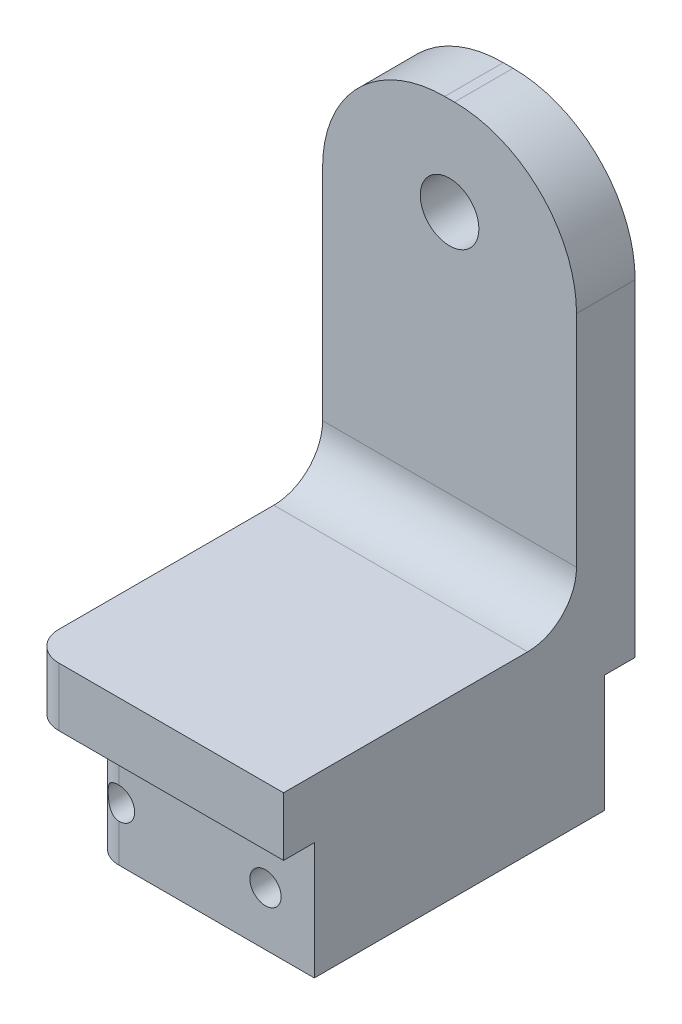
SolidWorks part; units mm, degrees
ref_plane "Front Plane" through (0, 0, 0) normal (0, 0, 1) x (1, 0, 0)
ref_plane "Top Plane" through (0, 0, 0) normal (0, 1, 0) x (1, 0, 0)
ref_plane "Right Plane" through (0, 0, 0) normal (1, 0, 0) x (0, 0, -1)
sketch "Sketch1" plane through (0, -44, 0) normal (0, 1, 0) x (1, 0, 0)
  line L0 (50.2641, 25) -> (50.2641, 28) construction
  line L1 (50.2641, -8) -> (50.2641, 28)
  line L2 (50.2641, -8) -> (27.2641, -8) construction
  line L3 (50.2641, -8) -> (27.2641, -8)
  line L4 (24.2641, -5) -> (24.2641, 25)
  line L5 (27.2641, 28) -> (50.2641, 28)
  arc A0 (27.2641, 28) -> (24.2641, 25) centre (27.2641, 25) ccw construction
  arc A1 (24.2641, -5) -> (27.2641, -8) centre (27.2641, -5) ccw construction
  arc A2 (27.2641, 28) -> (24.2641, 25) centre (27.2641, 25) ccw
  arc A3 (24.2641, -5) -> (27.2641, -8) centre (27.2641, -5) ccw
extrude "Boss-Extrude1" add sketch "Sketch1" along normal blind 6
sketch "Sketch2" plane through (0, -38, 0) normal (0, 1, 0) x (1, 0, 0)
  line L0 (24.2641, 25) -> (24.2641, -5) construction
  line L1 (50.2641, 28) -> (24.2641, 28)
  line L2 (50.2641, 28) -> (50.2641, 22)
  line L3 (50.2641, 22) -> (24.2641, 22)
  line L4 (24.2641, 28) -> (24.2641, 22)
  dimension "D1" = 6
extrude "Boss-Extrude2" add sketch "Sketch2" along normal blind 40
fillet "Fillet1" radius 12.5 2 edges at (24.2641, 2, -25) (50.2641, 2, -25)
sketch "Sketch3" plane through (0, 0, -22) normal (0, 0, 1) x (1, 0, 0)
  circle A0 centre (37.2641, -8) radius 3
extrude "Cut-Extrude1" cut sketch "Sketch3" against normal through all
sketch "Sketch4" plane through (0, -44, 0) normal (0, -1, 0) x (1, 0, 0)
  line L3 (50.2641, 4.85) -> (50.2641, -24.85)
  line L6 (50.2641, -24.85) -> (30.2641, -24.85)
  line L7 (27.4141, 2) -> (27.4141, -22)
  line L8 (30.2641, 4.85) -> (50.2641, 4.85)
  arc A4 (27.4141, -22) -> (30.2641, -24.85) centre (30.2641, -22) ccw
  arc A5 (30.2641, 4.85) -> (27.4141, 2) centre (30.2641, 2) ccw
extrude "Boss-Extrude3" add sketch "Sketch4" along normal blind 12
fillet "Fillet2" radius 5 1 edges at (37.2641, -38, -22)
sketch "Sketch5" plane through (0, 0, -24.85) normal (0, 0, -1) x (-1, 0, 0)
  circle A0 centre (-45.2641, -50.5) radius 1.6
  circle A1 centre (-30.2641, -50.5) radius 1.6
extrude "Cut-Extrude2" cut sketch "Sketch5" against normal through all
sketch "Sketch6" plane through (0, -38, 0) normal (0, -1, 0) x (1, 0, 0)
  line L2 (24.2641, -28) -> (27.2641, -28)
  line L3 (24.2641, -25) -> (24.2641, -28)
  line L4 (24.2641, -28) -> (27.2641, -28)
  line L5 (24.2641, -25) -> (24.2641, -28)
  arc A1 (24.2641, -25) -> (27.2641, -28) centre (27.2641, -25) ccw
  arc A2 (24.2641, -25) -> (27.2641, -28) centre (27.2641, -25) ccw
  dimension "D1" = 0
extrude "Cut-Extrude3" cut sketch "Sketch6" against normal through all
